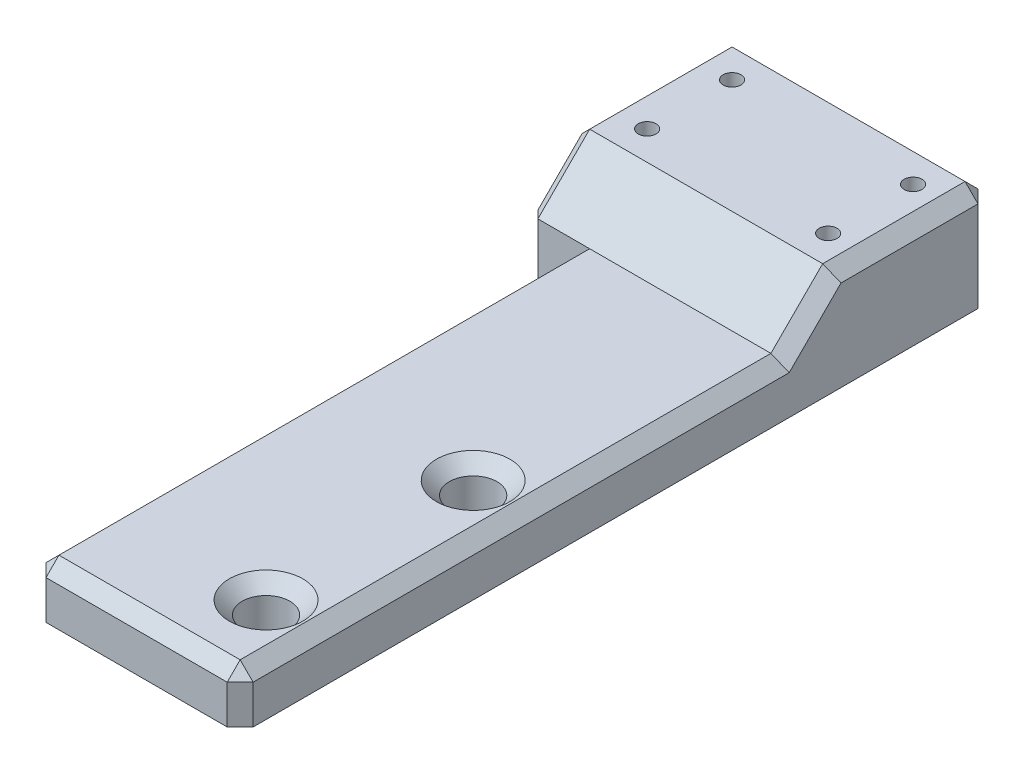
SolidWorks part; units mm, degrees
ref_plane "Front Plane" through (0, 0, 0) normal (0, 0, 1) x (1, 0, 0)
ref_plane "Top Plane" through (0, 0, 0) normal (0, 1, 0) x (1, 0, 0)
ref_plane "Right Plane" through (0, 0, 0) normal (1, 0, 0) x (0, 0, -1)
sketch "Sketch1" plane through (0, 0, 0) normal (0, 1, 0) x (1, 0, 0)
  line L1 (0, 0) -> (31.75, 0)
  line L2 (0, 0) -> (0, 92.075)
  line L3 (0, 92.075) -> (31.75, 92.075)
  line L4 (31.75, 0) -> (31.75, 92.075)
  circle A0 centre (25.4, 9.525) radius 2.921
  circle A1 centre (25.4, 34.925) radius 2.921
  dimension "D3" = 5.842
  dimension "D1" = 31.75
  dimension "D2" = 6.35
  dimension "0.375" = 9.525
  dimension "D4" = 25.4
  dimension "D5" = 57.15
extrude "Boss-Extrude1" add sketch "Sketch1" along normal blind 12.7
sketch "Sketch2" plane through (31.75, 0, 0) normal (1, 0, 0) x (0, 0, -1)
  line L0 (92.075, 12.7) -> (92.075, 0) construction
  line L1 (0, 12.7) -> (66.675, 12.7)
  line L2 (0, 12.7) -> (0, 6.35)
  line L3 (0, 6.35) -> (66.675, 6.35)
  line L4 (66.675, 12.7) -> (66.675, 6.35)
  dimension "D1" = 25.4
  dimension "D2" = 6.35
extrude "Cut-Extrude1" cut sketch "Sketch2" against normal through all
sketch "Sketch3" plane through (0, 0, 0) normal (0, -1, 0) x (1, 0, 0)
  line L0 (0, -92.075) -> (0, 0) construction
  line L2 (31.75, -92.075) -> (0, -92.075) construction
  line L3 (0, 0) -> (6.35, 0)
  line L4 (0, 0) -> (0, -66.675)
  line L5 (0, -66.675) -> (6.35, -66.675)
  line L6 (6.35, 0) -> (6.35, -66.675)
  circle A0 centre (27.2796, -76.581) radius 1.0922
  circle A1 centre (5.08, -86.995) radius 1.0922
  circle A2 centre (27.2796, -86.995) radius 1.0922
  circle A3 centre (5.08, -76.581) radius 1.0922
  point P17 (0, 0)
  point P18 (0, 0)
  point P19 (0, 0)
  point P20 (0, 0)
  point P21 (0, 0)
  point P22 (0, 0)
  point P23 (0, 0)
  dimension "D1" = 2.1844
  dimension "D2" = 22.1996
  dimension "D3" = 5.08
  dimension "D4" = 5.08
  dimension "D5" = 6.35
  dimension "D6" = 10.414
  dimension "2.625" = 66.675
extrude "Cut-Extrude2" cut sketch "Sketch3" against normal through all
chamfer "Chamfer1" distance 6.35 angle 45 1 edges at (15.875, 12.7, -66.675)
chamfer "Chamfer2" distance 1.5875 angle 45 15 edges at (25.4, 6.35, -12.446) (25.4, 6.35, -37.846) (31.75, 6.35, -92.075) (31.75, 3.175, 0) (6.35, 3.175, 0) (6.35, 6.35, -33.3375) (19.05, 6.35, 0) (31.75, 6.35, -33.3375) (31.75, 9.525, -69.85) (31.75, 12.7, -82.55) (0, 6.35, -92.075) (15.875, 12.7, -92.075) (0, 12.7, -82.55) (0, 9.525, -69.85) (0, 3.175, -66.675)
